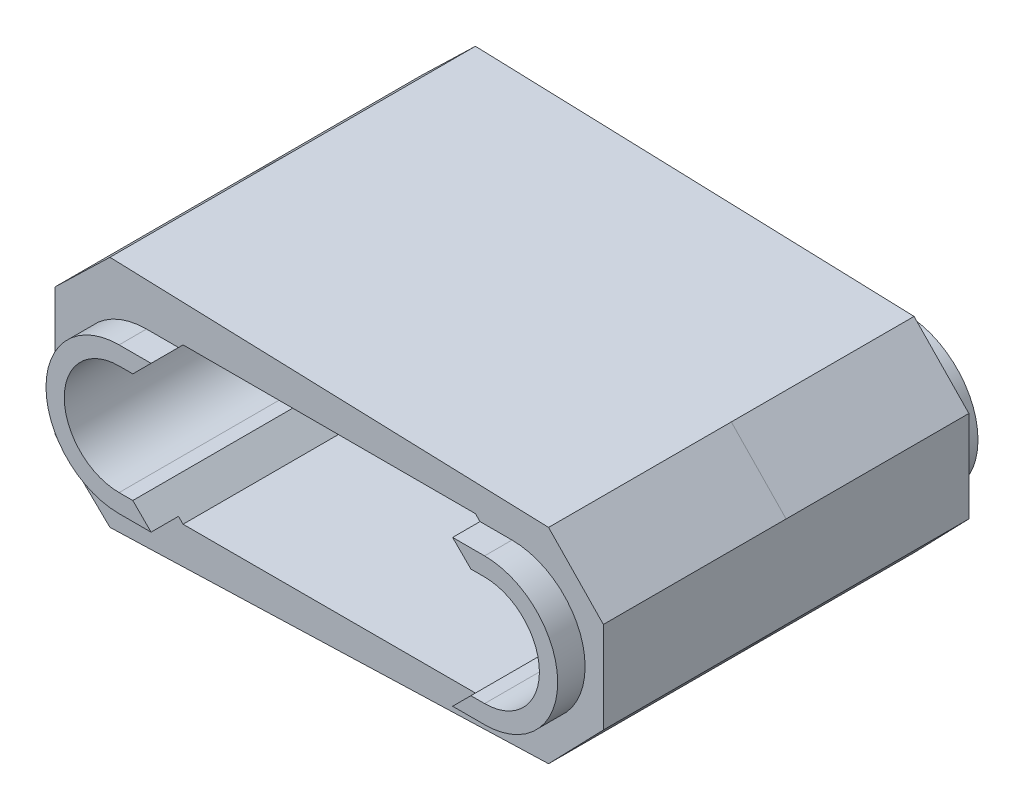
SolidWorks part; units mm, degrees
ref_plane "Front Plane" through (0, 0, 0) normal (0, 0, 1) x (1, 0, 0)
ref_plane "Top Plane" through (0, 0, 0) normal (0, 1, 0) x (1, 0, 0)
ref_plane "Right Plane" through (0, 0, 0) normal (1, 0, 0) x (0, 0, -1)
sketch "Sketch1" plane through (0, 0, 0) normal (0, 0, 1) x (1, 0, 0)
  line L0 (0, 0) -> (25, 0) construction
  line L1 (0, 6.5) -> (30, 5.5)
  line L2 (0, -6.5) -> (30, -5.5)
  line L3 (5, 0) -> (25, 0) construction
  line L4 (5, 3) -> (25, 3)
  line L5 (5, -3) -> (25, -3)
  line L6 (0, 6.5) -> (0, -6.5)
  line L7 (30, 5.5) -> (30, -5.5)
  line L8 (5, 4) -> (25, 4)
  line L9 (5, -4) -> (25, -4)
  arc A3 (5, 3) -> (5, -3) centre (5, 0) ccw
  arc A4 (25, -3) -> (25, 3) centre (25, 0) ccw
  arc A5 (25, -4) -> (25, 4) centre (25, 0) ccw
  arc A6 (5, 4) -> (5, -4) centre (5, 0) ccw
  point P3 (30, 0)
  point P7 (15, 0)
  point P15 (28, 0)
  point P20 (0, 0)
  point P23 (2, 0)
  dimension "D5" = 2
  dimension "D1" = 13
  dimension "D2" = 11
  dimension "D3" = 2
  dimension "D4" = 20
  dimension "D6" = 30
  dimension "D7" = 1
extrude "Boss-Extrude1" add sketch "Sketch1" along normal blind 10 contours L7 L1 L6 L2 A6 L8 A5 L9 | L8 A6 L9 A5 A4 L5 A3 L4 region at (14.9891, 5.6732, 0) region at (15, 3.7088, 0)
chamfer "Chamfer1" distance 3 distance2 3 4 edges at (0, -6.5, 5) (0, 6.5, 5) (30, -5.5, 5) (30, 5.5, 5)
extrude "Boss-Extrude2" add sketch "Sketch1<4>" against normal blind 1.5 contours L8 A6 L9 A5 A4 L5 A3 L4 region at (15, 3.7088, 0)
sketch "Sketch1<4>" plane through (0, 0, 0) normal (0, 0, 1) x (1, 0, 0) same geometry as "Sketch1"
mirror "Mirror1" about plane through (0, 0, 10) normal (0, 0, 1) of "Boss-Extrude1", "Chamfer1", "Boss-Extrude2"
sketch "Sketch2" plane through (0, 0, 21.5) normal (0, 0, 1) x (1, 0, 0)
  line L0 (5, 3) -> (25, 3) construction
  line L1 (7, 4.25) -> (23, 4.25)
  line L2 (7, 4.25) -> (7, -4.25)
  line L3 (7, -4.25) -> (23, -4.25)
  line L4 (23, 4.25) -> (23, -4.25)
  line L5 (7, 4.25) -> (23, -4.25) construction
  line L6 (7, -4.25) -> (23, 4.25) construction
  point P0 (15, 0)
  point P5 (15.2877, 0)
  point P6 (14.5326, 0)
  point P7 (15.3775, 0)
  point P9 (14.6584, 0)
  point P12 (15, 3)
  dimension "D1" = 8.5
  dimension "D2" = 16
extrude "Cut-Extrude1" cut sketch "Sketch2" against normal through all
chamfer "Chamfer2" distance 1.25 4 edges at (23, 3, 10) (23, -3, 10) (7, -3, 10) (7, 3, 10)
